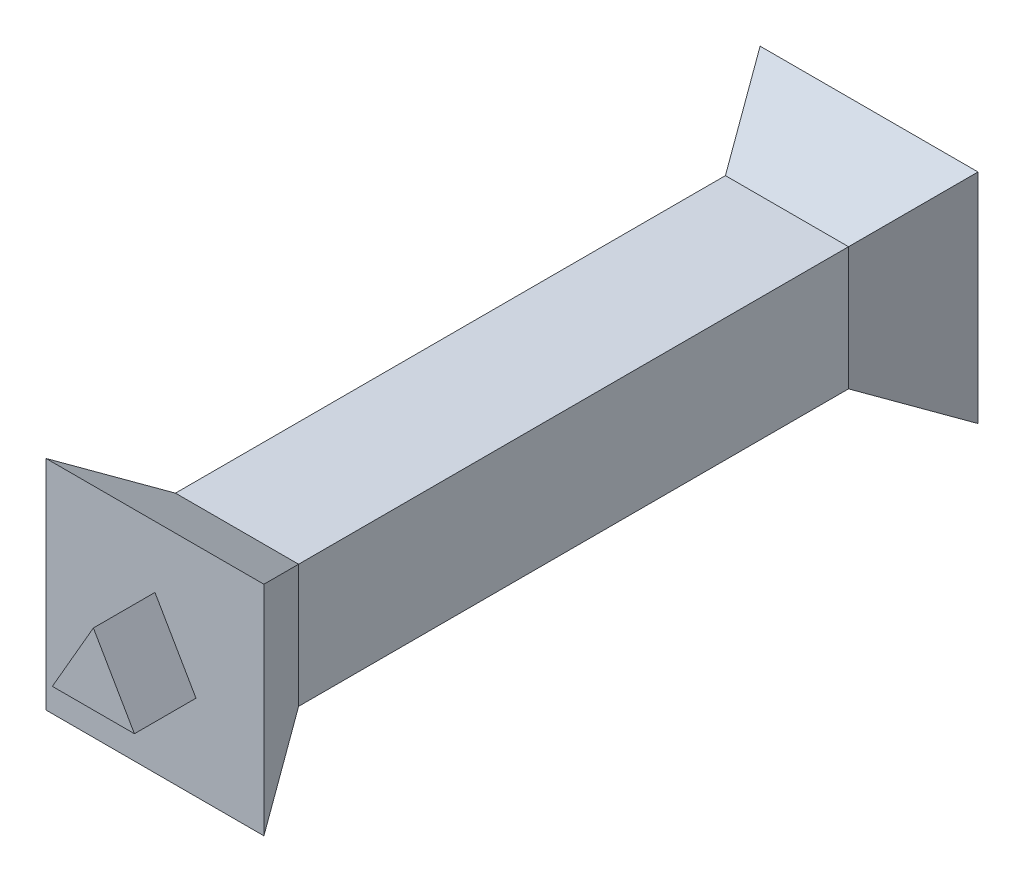
SolidWorks part; units mm, degrees
ref_plane "Front Plane" through (0, 0, 0) normal (0, 0, 1) x (1, 0, 0)
ref_plane "Top Plane" through (0, 0, 0) normal (0, 1, 0) x (1, 0, 0)
ref_plane "Right Plane" through (0, 0, 0) normal (1, 0, 0) x (0, 0, -1)
sketch "Sketch1" plane through (0, 0, 0) normal (0, 0, 1) x (1, 0, 0)
  line L1 (-1.5, 1.5) -> (1.5, 1.5)
  line L2 (-1.5, 1.5) -> (-1.5, -1.5)
  line L3 (-1.5, -1.5) -> (1.5, -1.5)
  line L4 (1.5, 1.5) -> (1.5, -1.5)
  line L5 (-1.5, 1.5) -> (1.5, -1.5) construction
  line L6 (-1.5, -1.5) -> (1.5, 1.5) construction
  point P0 (0, 0)
  dimension "D1" = 3
extrude "Boss-Extrude1" add sketch "Sketch1" along normal blind 13.4
ref_plane "Plane1" through (0, 0, 6.7) normal (0, 0, 1) x (1, 0, 0)
sketch "Sketch2" plane through (0, 0, 13.4) normal (0, 0, 1) x (1, 0, 0)
  line L4 (1.5, -1.5) -> (1.5, 1.5)
  line L5 (1.5, 1.5) -> (-1.5, 1.5)
  line L6 (-1.5, 1.5) -> (-1.5, -1.5)
  line L7 (-1.5, -1.5) -> (1.5, -1.5)
  line L8 (1.5, -1.5) -> (1.5, 1.5)
  line L9 (1.5, 1.5) -> (-1.5, 1.5)
  line L10 (-1.5, 1.5) -> (-1.5, -1.5)
  line L11 (-1.5, -1.5) -> (1.5, -1.5)
  dimension "D1" = 0
extrude "Boss-Extrude2" add sketch "Sketch2" along normal blind 2 draft 30 draft outward yes
mirror "Mirror1" about plane through (0, 0, 6.7) normal (0, 0, 1) of "Boss-Extrude2"
sketch "Sketch3" plane through (0, 0, 15.4) normal (0, 0, 1) x (1, 0, 0)
  line L0 (0, 1.1547) -> (-1, -0.5774)
  line L1 (-1, -0.5774) -> (1, -0.5774)
  line L2 (1, -0.5774) -> (0, 1.1547)
  line L3 (0, 1.1547) -> (0, -0.5774) construction
  line L4 (-0.5, 0.2887) -> (1, -0.5774) construction
  line L5 (-1, -0.5774) -> (0.5, 0.2887) construction
  point P5 (0, 0)
  point P7 (0, 0.9334)
  dimension "D1" = 2
extrude "Boss-Extrude3" add sketch "Sketch3" along normal blind 1.5
mirror "Mirror2" about plane through (0, 0, 6.7) normal (0, 0, 1) of "Boss-Extrude3"
